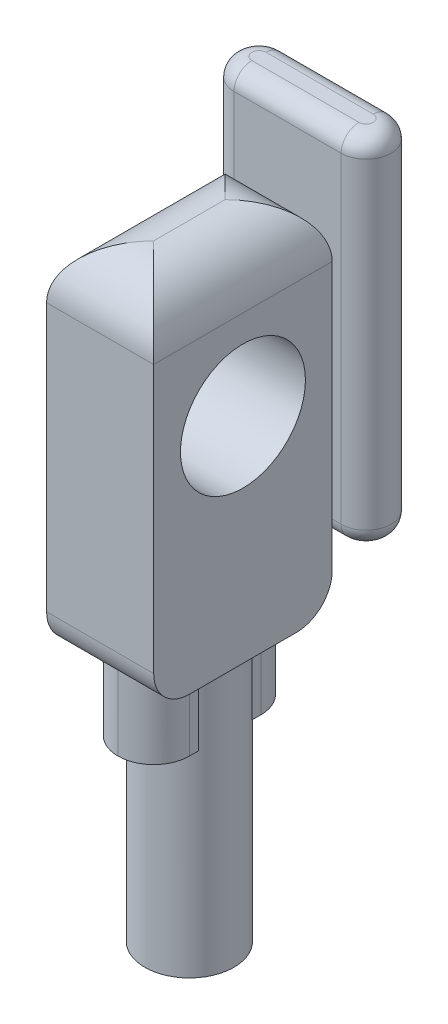
SolidWorks part; units mm, degrees
ref_plane "Front Plane" through (0, 0, 0) normal (0, 0, 1) x (1, 0, 0)
ref_plane "Top Plane" through (0, 0, 0) normal (0, 1, 0) x (1, 0, 0)
ref_plane "Right Plane" through (0, 0, 0) normal (1, 0, 0) x (0, 0, -1)
sketch "Sketch1" plane through (0, 0, 0) normal (1, 0, 0) x (0, 0, -1)
  line L1 (-7.62, -12.7) -> (7.62, -12.7)
  line L2 (-7.62, -12.7) -> (-7.62, 12.7)
  line L3 (-7.62, 12.7) -> (7.62, 12.7)
  line L4 (7.62, -12.7) -> (7.62, 12.7)
  line L5 (-7.62, -12.7) -> (7.62, 12.7) construction
  line L6 (-7.62, 12.7) -> (7.62, -12.7) construction
  point P0 (0, 0)
  dimension "D1" = 25.4
  dimension "D2" = 15.24
extrude "Boss-Extrude1" add sketch "Sketch1" along normal mid plane 10.16
fillet "Fillet1" radius 2.54 12 edges at (0, -12.7, -7.62) (0, 12.7, -7.62) (0, 12.7, 7.62) (0, -12.7, 7.62) (-5.08, 12.7, 0) (-5.08, 0, 7.62) (-5.08, -12.7, 0) (-5.08, 0, -7.62) (5.08, -12.7, 0) (5.08, 0, 7.62) (5.08, 12.7, 0) (5.08, 0, -7.62)
sketch "Sketch2" plane through (5.08, 0, 0) normal (1, 0, 0) x (0, 0, -1)
  line L0 (0, 6.985) -> (0, -6.985) construction
  circle A0 centre (0, 6.985) radius 3.175
  circle A1 centre (0, -6.985) radius 3.175
  point P3 (0, 0)
  dimension "D2" = 6.35
  dimension "D1" = 13.97
extrude "Boss-Extrude2" add sketch "Sketch2" along normal blind 6.35
mirror "Mirror1" about plane through (0, 0, 0) normal (1, 0, 0) of "Boss-Extrude2"
sketch "Sketch3" plane through (0, 12.7, 0) normal (0, 1, 0) x (1, 0, 0)
  line L0 (2.54, 5.08) -> (-2.54, 5.08) construction
  line L1 (-2.54, 5.08) -> (2.54, 5.08)
  line L2 (-2.54, 5.08) -> (-2.54, -5.08)
  line L3 (-2.54, -5.08) -> (2.54, -5.08)
  line L4 (2.54, 5.08) -> (2.54, -5.08)
  line L5 (-2.54, 5.08) -> (-2.54, -5.08) construction
extrude "Boss-Extrude3" add sketch "Sketch3" along normal blind 5.08
sketch "Sketch4" plane through (0, 17.78, 0) normal (0, 1, 0) x (1, 0, 0)
  line L0 (2.54, 5.08) -> (-2.54, 5.08) construction
  line L1 (-3.81, -6.35) -> (3.81, -6.35)
  line L2 (-3.81, -6.35) -> (-3.81, 6.35)
  line L3 (-3.81, 6.35) -> (3.81, 6.35)
  line L4 (3.81, -6.35) -> (3.81, 6.35)
  line L5 (-3.81, -6.35) -> (3.81, 6.35) construction
  line L6 (-3.81, 6.35) -> (3.81, -6.35) construction
  line L7 (2.54, -5.08) -> (2.54, 5.08) construction
  point P0 (0, 0)
  dimension "D1" = 1.27
  dimension "D2" = 1.27
extrude "Boss-Extrude4" add sketch "Sketch4" along normal blind 25.4
fillet "Fillet2" radius 2.54 2 edges at (0, 17.78, -6.35) (0, 17.78, 6.35)
fillet "Fillet3" radius 3.81 4 edges at (0, 43.18, 6.35) (-3.81, 43.18, 0) (0, 43.18, -6.35) (3.81, 43.18, 0)
sketch "Sketch5" plane through (0, 0, -6.35) normal (0, 0, -1) x (-1, 0, 0)
  line L0 (0, 39.37) -> (0, 25.4) construction
  line L1 (3.81, 39.37) -> (-3.81, 39.37) construction
  circle A0 centre (0, 32.385) radius 1.905
  circle A1 centre (0, 25.4) radius 1.905
  dimension "D2" = 3.81
  dimension "D1" = 13.97
extrude "Boss-Extrude5" add sketch "Sketch5" along normal blind 1.27
ref_plane "Plane1" through (0, 21.59, 0) normal (0, 1, 0) x (1, 0, 0)
sketch "Sketch6" plane through (0, 21.59, 0) normal (0, 1, 0) x (1, 0, 0)
  line L0 (-3.81, 8.763) -> (3.81, 8.763) construction
  line L1 (-3.81, 10.541) -> (3.81, 10.541)
  line L2 (-3.81, 6.985) -> (3.81, 6.985)
  line L3 (1.905, 7.62) -> (-1.905, 7.62) construction
  arc A0 (-3.81, 10.541) -> (-3.81, 6.985) centre (-3.81, 8.763) ccw
  arc A1 (3.81, 6.985) -> (3.81, 10.541) centre (3.81, 8.763) ccw
  point P2 (0, 8.763)
  dimension "D1" = 3.556
  dimension "D2" = 7.62
  dimension "D3" = 0.635
extrude "Boss-Extrude6" add sketch "Sketch6" along normal blind 25.4
fillet "Fillet4" radius 1.27 8 edges at (0, 21.59, -6.985) (5.588, 21.59, -8.763) (0, 21.59, -10.541) (-5.588, 21.59, -8.763) (0, 46.99, -10.541) (5.588, 46.99, -8.763) (0, 46.99, -6.985) (-5.588, 46.99, -8.763)
sketch "Sketch7" plane through (0, 0, -10.541) normal (0, 0, -1) x (-1, 0, 0)
  line L0 (3.81, 45.72) -> (-3.81, 45.72) construction
  line L1 (-2.794, 23.495) -> (2.794, 23.495)
  line L2 (-2.794, 23.495) -> (-2.794, 45.085)
  line L3 (-2.794, 45.085) -> (2.794, 45.085)
  line L4 (2.794, 23.495) -> (2.794, 45.085)
  line L5 (-2.794, 23.495) -> (2.794, 45.085) construction
  line L6 (-2.794, 45.085) -> (2.794, 23.495) construction
  line L8 (3.81, 45.72) -> (3.81, 22.86) construction
  line L9 (-3.81, 22.86) -> (3.81, 22.86) construction
  point P0 (0, 34.29)
  dimension "D1" = 0.635
  dimension "D2" = 1.016
  dimension "D3" = 0.635
extrude "Cut-Extrude1" cut sketch "Sketch7" against normal blind 1.016
fillet "Fillet5" radius 0.254 4 edges at (0, 23.495, -10.541) (-2.794, 34.29, -10.541) (2.794, 34.29, -10.541) (0, 45.085, -10.541)
sketch "Sketch8" plane through (3.81, 0, 0) normal (1, 0, 0) x (0, 0, -1)
  line L0 (6.35, 39.37) -> (-6.35, 39.37) construction
  circle A0 centre (0, 33.02) radius 4.445
  point P2 (0, 39.37)
  dimension "D1" = 8.89
  dimension "D2" = 6.35
extrude "Cut-Extrude2" cut sketch "Sketch8" against normal up to next
fillet "Fillet6" radius 0.635 4 edges at (-11.43, -6.985, -3.175) (-11.43, 6.985, -3.175) (11.43, -6.985, -3.175) (11.43, 6.985, -3.175)
sketch "Sketch9" plane through (11.43, 0, 0) normal (1, 0, 0) x (0, 0, -1)
  line L0 (-5.08, 12.7) -> (5.08, 12.7) construction
  line L1 (-7.62, -12.7) -> (7.62, -12.7)
  line L2 (-7.62, -12.7) -> (-7.62, 12.7)
  line L3 (-7.62, 12.7) -> (7.62, 12.7)
  line L4 (7.62, -12.7) -> (7.62, 12.7)
  line L5 (-7.62, -12.7) -> (7.62, 12.7) construction
  line L6 (-7.62, 12.7) -> (7.62, -12.7) construction
  line L7 (-7.62, -10.16) -> (-7.62, 10.16) construction
  point P0 (0, 0)
extrude "Cut-Extrude3" cut sketch "Sketch9" against normal up to next
sketch "Sketch10" plane through (0, 12.7, 0) normal (0, -1, 0) x (1, 0, 0)
  circle A0 centre (0, 0) radius 3.175
  dimension "D1" = 6.35
extrude "Boss-Extrude7" add sketch "Sketch10" along normal blind 13.97 and the other way blind 5.08
fillet "Fillet7" radius 2.54 4 edges at (-2.54, 15.4101, 5.08) (2.54, 15.4101, 5.08) (-2.54, 15.4101, -5.08) (2.54, 15.4101, -5.08)
